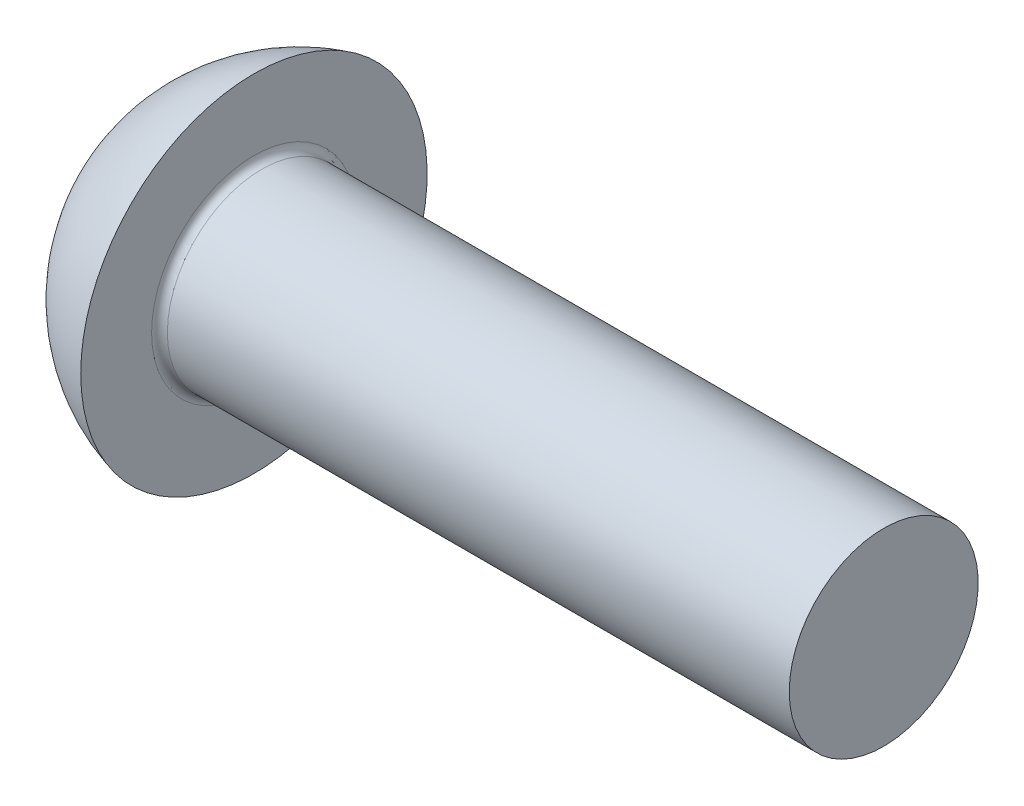
SolidWorks part; units mm, degrees
ref_plane "Front" through (0, 0, 0) normal (0, 0, 1) x (1, 0, 0)
ref_plane "Top" through (0, 0, 0) normal (0, 1, 0) x (1, 0, 0)
ref_plane "Right" through (0, 0, 0) normal (1, 0, 0) x (0, 0, -1)
sketch "Sketch1" plane through (29.2835, 18.2835, 0) normal (0, 0, 1) x (0, 1, 0)
  line L0 (-18.2835, -19.2165) -> (-18.2835, 29.2835)
  line L1 (-7.2835, 20.7835) -> (-12.2835, 20.7835)
  line L2 (-12.2835, 20.7835) -> (-12.2835, -19.2165)
  line L3 (-18.2835, -19.2165) -> (-12.2835, -19.2165)
  line L4 (-18.2835, -12.7268) -> (-18.2835, -20.1495) construction
  arc A0 (-18.2835, 29.2835) -> (-7.2835, 20.7835) centre (-18.2835, 17.9159) cw
  dimension "l" = 40
  dimension "K" = 8.5
  dimension "d" = 12
  dimension "dk" = 22
revolve "Base-Revolve" add sketch "Sketch1" angle 360 about L4
fillet "Fillet1" radius 0.5 1 edges at (8.5, 0, 6)
